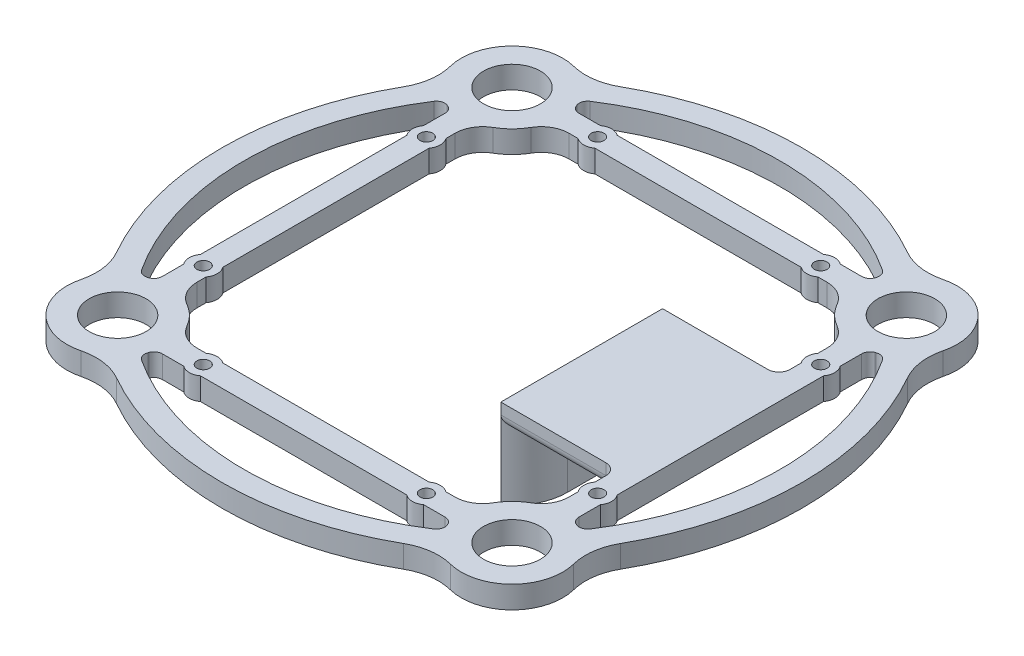
SolidWorks part; units mm, degrees
ref_plane "Front Plane" through (0, 0, 0) normal (0, 0, 1) x (1, 0, 0)
ref_plane "Top Plane" through (0, 0, 0) normal (0, 1, 0) x (1, 0, 0)
ref_plane "Right Plane" through (0, 0, 0) normal (1, 0, 0) x (0, 0, -1)
sketch "Sketch1" plane through (0, 0, 0) normal (0, 1, 0) x (1, 0, 0)
  line L1 (-35.3553, -35.3553) -> (35.3553, -35.3553) construction
  line L2 (-35.3553, -35.3553) -> (-35.3553, 35.3553) construction
  line L3 (-35.3553, 35.3553) -> (35.3553, 35.3553) construction
  line L4 (35.3553, -35.3553) -> (35.3553, 35.3553) construction
  line L5 (-35.3553, -35.3553) -> (35.3553, 35.3553) construction
  line L6 (-35.3553, 35.3553) -> (35.3553, -35.3553) construction
  circle A0 centre (0, 0) radius 52
  circle A1 centre (0, 0) radius 50 construction
  circle A2 centre (0, 0) radius 48
  circle A3 centre (35.3553, 35.3553) radius 5.1
  circle A4 centre (35.3553, 35.3553) radius 9.1
  circle A5 centre (-35.3553, 35.3553) radius 9.1
  circle A6 centre (-35.3553, 35.3553) radius 5.1
  circle A7 centre (-35.3553, -35.3553) radius 9.1
  circle A8 centre (-35.3553, -35.3553) radius 5.1
  circle A9 centre (35.3553, -35.3553) radius 5.1
  circle A10 centre (35.3553, -35.3553) radius 9.1
  dimension "D1" = 96
  dimension "D2" = 100
  dimension "D3" = 104
  dimension "D4" = 10.2
  dimension "D5" = 10.2
  dimension "D6" = 10.2
  dimension "D7" = 10.2
  dimension "D8" = 18.2
  dimension "D9" = 18.2
  dimension "D10" = 18.2
  dimension "D11" = 18.2
extrude "Boss-Extrude1" add sketch "Sketch1" along normal blind 4 contours A7 A2 A5 A0 | A5 A2 A4 A0 | A10 A0 A4 A2 | A10 A2 A7 A0 | A8 A2 A7 | A8 A2 A7 A0 | A8 A0 A7 | A8 A0 A7 A2 | A2 A10 A9 | A0 A10 A2 A9 | A0 A10 A9 | A2 A10 A0 A9 | A0 A4 A2 A3 | A2 A4 A0 A3 | A0 A4 A3 | A2 A4 A3 | A6 A2 A5 A0 | A6 A0 A5 A2 | A6 A0 A5 | A6 A2 A5 region at (49.0102, 0, 15.4585) region at (39.943, 0, -30.075) region at (39.073, 0, -39.073) region at (39.073, 0, 39.073) region at (39.943, 0, 30.075) region at (31.3721, 0, -31.3721) region at (31.3721, 0, 31.3721) region at (30.075, 0, -39.943) region at (0, 0, -48.6096) region at (30.075, 0, 39.943) region at (0, 0, 51.3904) region at (-31.3721, 0, -31.3721) region at (-30.075, 0, -39.943) region at (-39.073, 0, -39.073) region at (-39.073, 0, 39.073) region at (-30.075, 0, 39.943) region at (-31.3721, 0, 31.3721) region at (-41.5843, 0, -27.9071) region at (-39.943, 0, -30.075) region at (-39.943, 0, 30.075)
sketch "Sketch2" plane through (0, 4, 0) normal (0, 1, 0) x (1, 0, 0)
  line L0 (-33.3553, 26.4778) -> (-33.3553, -26.4778)
  line L1 (35.3553, -35.3553) -> (-35.3553, -35.3553) construction
  line L2 (35.3553, -35.3553) -> (35.3553, 35.3553) construction
  line L3 (35.3553, 35.3553) -> (-35.3553, 35.3553) construction
  line L4 (-35.3553, -35.3553) -> (-35.3553, 35.3553) construction
  line L5 (35.3553, -35.3553) -> (-35.3553, 35.3553) construction
  line L6 (35.3553, 35.3553) -> (-35.3553, -35.3553) construction
  line L7 (-37.3553, 26.4778) -> (-37.3553, -26.4778)
  line L8 (-26.4778, 37.3553) -> (26.4778, 37.3553)
  line L9 (-26.4778, 33.3553) -> (26.4778, 33.3553)
  line L10 (37.3553, 26.4778) -> (37.3553, -26.4778)
  line L11 (33.3553, 26.4778) -> (33.3553, -26.4778)
  line L12 (-26.4778, -33.3553) -> (26.4778, -33.3553)
  line L13 (-26.4778, -37.3553) -> (26.4778, -37.3553)
  arc A0 (-39.5091, 27.2586) -> (-27.2586, 39.5091) centre (-35.3553, 35.3553) ccw construction
  arc A1 (-27.2586, -39.5091) -> (-39.5091, -27.2586) centre (-35.3553, -35.3553) ccw construction
  arc A2 (27.2586, 39.5091) -> (39.5091, 27.2586) centre (35.3553, 35.3553) ccw construction
  arc A3 (39.5091, -27.2586) -> (27.2586, -39.5091) centre (35.3553, -35.3553) ccw construction
  circle A4 centre (-35.3553, 35.3553) radius 9.1
  circle A5 centre (35.3553, 35.3553) radius 9.1
  circle A6 centre (35.3553, -35.3553) radius 9.1
  circle A7 centre (-35.3553, -35.3553) radius 9.1
  point P0 (0, 0)
  arc M14 (-27.2586, -39.5091) -> (-39.5091, -27.2586) centre (-35.3553, -35.3553) ccw
  arc M16 (-39.5091, 27.2586) -> (-27.2586, 39.5091) centre (-35.3553, 35.3553) ccw
  arc M18 (27.2586, 39.5091) -> (39.5091, 27.2586) centre (35.3553, 35.3553) ccw
  arc M20 (39.5091, -27.2586) -> (27.2586, -39.5091) centre (35.3553, -35.3553) ccw
  dimension "D1" = 2
  dimension "D2" = 2
  dimension "D3" = 2
  dimension "D4" = 2
  dimension "D5" = 2
  dimension "D6" = 2
  dimension "D7" = 2
  dimension "D8" = 2
extrude "Boss-Extrude2" add sketch "Sketch2" against normal blind 4 contours L9 L8 M16 M18 | L7 L0 M16 M14 | L11 L10 M18 M20 | L13 L12 M14 M20 region at (-35.3553, 4, 0) region at (0, 4, -35.3553) region at (0, 4, 35.3553) region at (35.3553, 4, 0)
sketch "Sketch3" plane through (0, 4, 0) normal (0, 1, 0) x (1, 0, 0)
  line L0 (-26.4778, 33.3553) -> (26.4778, 33.3553) construction
  line L1 (-35.3553, 20) -> (35.3553, 20) construction
  line L2 (-35.3553, 20) -> (-35.3553, -20) construction
  line L3 (-35.3553, -20) -> (35.3553, -20) construction
  line L4 (35.3553, 20) -> (35.3553, -20) construction
  line L5 (-35.3553, 20) -> (35.3553, -20) construction
  line L6 (-35.3553, -20) -> (35.3553, 20) construction
  line L7 (20, -35.3553) -> (-20, -35.3553) construction
  line L8 (20, -35.3553) -> (20, 35.3553) construction
  line L9 (20, 35.3553) -> (-20, 35.3553) construction
  line L10 (-20, -35.3553) -> (-20, 35.3553) construction
  line L11 (20, -35.3553) -> (-20, 35.3553) construction
  line L12 (20, 35.3553) -> (-20, -35.3553) construction
  line L13 (-33.3553, 26.4778) -> (-33.3553, -26.4778) construction
  circle A0 centre (-20, 35.3553) radius 2.5
  circle A1 centre (20, 35.3553) radius 2.5
  circle A2 centre (35.3553, 20) radius 2.5
  circle A3 centre (35.3553, -20) radius 2.5
  circle A4 centre (-35.3553, -20) radius 2.5
  circle A5 centre (-35.3553, 20) radius 2.5
  circle A6 centre (-20, -35.3553) radius 2.5
  circle A7 centre (20, -35.3553) radius 2.5
  point P0 (0, 0)
  point P6 (0, 0)
  dimension "D5" = 5
  dimension "D6" = 5
  dimension "D7" = 5
  dimension "D8" = 5
  dimension "D9" = 5
  dimension "D10" = 5
  dimension "D11" = 5
  dimension "D12" = 5
  dimension "D1" = 2
  dimension "D2" = 2
  dimension "D3" = 40
  dimension "D4" = 40
extrude "Boss-Extrude3" add sketch "Sketch3" against normal blind 4
sketch "Sketch4" plane through (0, 4, 0) normal (0, 1, 0) x (1, 0, 0)
  circle A0 centre (-20, 35.3553) radius 1.15
  circle A1 centre (20, 35.3553) radius 1.15
  circle A2 centre (-35.3553, 20) radius 1.15
  circle A3 centre (-35.3553, -20) radius 1.15
  circle A4 centre (-20, -35.3553) radius 1.15
  circle A5 centre (20, -35.3553) radius 1.15
  circle A6 centre (35.3553, -20) radius 1.15
  circle A7 centre (35.3553, 20) radius 1.15
  dimension "D1" = 2.3
  dimension "D2" = 2.3
  dimension "D3" = 2.3
  dimension "D4" = 2.3
  dimension "D5" = 2.3
  dimension "D6" = 2.3
  dimension "D7" = 2.3
  dimension "D8" = 2.3
extrude "Cut-Extrude1" cut sketch "Sketch4" against normal blind 4
fillet "Fillet1" radius 10 8 edges at (29.8349, 2, 42.5896) (42.5896, 2, 29.8349) (42.5896, 2, -29.8349) (29.8349, 2, -42.5896) (-29.8349, 2, -42.5896) (-42.5896, 2, -29.8349) (-42.5896, 2, 29.8349) (-29.8349, 2, 42.5896)
fillet "Fillet2" radius 1.5 16 edges at (-39.5091, 2, 27.2586) (-37.3553, 2, 26.4778) (-39.5091, 2, -27.2586) (-37.3553, 2, -26.4778) (27.2586, 2, -39.5091) (26.4778, 2, -37.3553) (-26.4778, 2, -37.3553) (-27.2586, 2, -39.5091) (39.5091, 2, 27.2586) (37.3553, 2, 26.4778) (37.3553, 2, -26.4778) (39.5091, 2, -27.2586) (27.2586, 2, 39.5091) (26.4778, 2, 37.3553) (-27.2586, 2, 39.5091) (-26.4778, 2, 37.3553)
fillet "Fillet3" radius 5 8 edges at (-26.4778, 2, -33.3553) (-33.3553, 2, -26.4778) (-33.3553, 2, 26.4778) (-26.4778, 2, 33.3553) (26.4778, 2, 33.3553) (33.3553, 2, 26.4778) (26.4778, 2, -33.3553) (33.3553, 2, -26.4778)
sketch "Sketch5" plane through (0, 4, 0) normal (0, 1, 0) x (1, 0, 0)
  line L5 (33.3553, 18.5) -> (33.3553, -18.5) construction
  line L6 (33.3553, 14.5) -> (12.4953, 14.5)
  line L7 (33.3553, 14.5) -> (33.3553, -14.5)
  line L8 (33.3553, -14.5) -> (12.4953, -14.5)
  line L9 (12.4953, 14.5) -> (12.4953, -14.5)
  circle A0 centre (35.3553, -20) radius 1.15 construction
  dimension "D1" = 20.86
  dimension "D2" = 29
  dimension "D3" = 5.5
extrude "Boss-Extrude4" add sketch "Sketch5" against normal blind 4
sketch "Sketch6" plane through (0, 0, 0) normal (0, -1, 0) x (1, 0, 0)
  line L0 (33.3553, -14.5) -> (12.4953, -14.5) construction
  line L1 (12.4953, 14.5) -> (16.4953, 14.5)
  line L2 (12.4953, 14.5) -> (12.4953, -14.5)
  line L3 (12.4953, -14.5) -> (16.4953, -14.5)
  line L4 (16.4953, 14.5) -> (16.4953, -14.5)
  dimension "D1" = 4
extrude "Boss-Extrude5" add sketch "Sketch6" along normal blind 12
fillet "Fillet4" radius 10 2 edges at (16.4953, -6, -14.5) (16.4953, -6, 14.5)
fillet "Fillet5" radius 2 6 edges at (33.3553, 0, 16.5) (33.3553, 0, -16.5) (22.9253, 0, 14.5) (22.9253, 0, -14.5) (33.3553, 2, -14.5) (33.3553, 2, 14.5)
